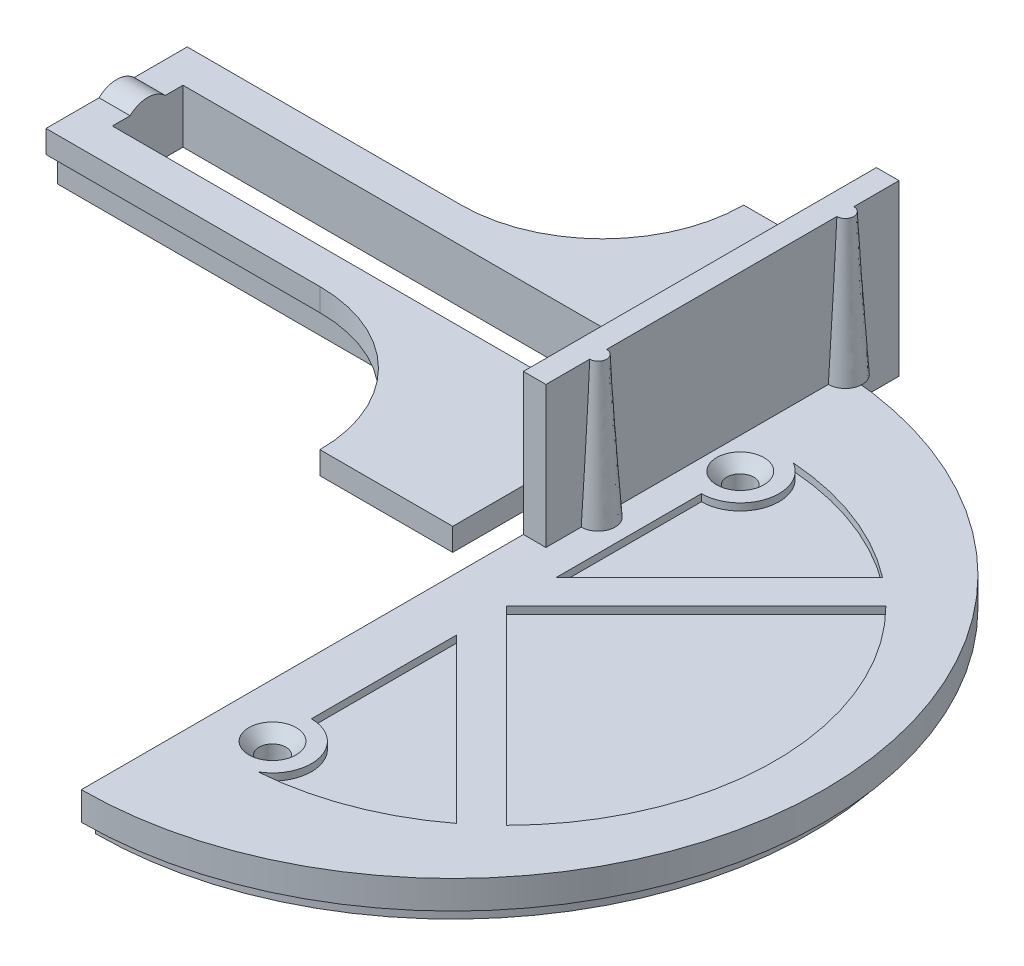
SolidWorks part; units mm, degrees
ref_plane "Alzado" through (0, 0, 0) normal (0, 0, 1) x (1, 0, 0)
ref_plane "Planta" through (0, 0, 0) normal (0, 1, 0) x (1, 0, 0)
ref_plane "Vista lateral" through (0, 0, 0) normal (1, 0, 0) x (0, 0, -1)
sketch "Sketch1" plane through (0, 0, 0) normal (1, 0, 0) x (0, 0, -1)
  line L1 (-10.668, -4.826) -> (10.668, -4.826)
  line L2 (-12.7, 0.762) -> (-12.7, 4.826)
  line L3 (-12.7, 4.826) -> (-3.1623, 4.826)
  line L6 (0, -4.826) -> (0, 12.0832) construction
  line L7 (-10.668, -4.826) -> (-10.668, 0.762)
  line L9 (-10.668, 0.762) -> (-12.7, 0.762)
  line L13 (10.668, 0.762) -> (12.7, 0.762)
  line L14 (10.668, -4.826) -> (10.668, 0.762)
  line L15 (12.7, 4.826) -> (3.1623, 4.826)
  line L16 (12.7, 0.762) -> (12.7, 4.826)
  arc A0 (3.1623, 4.826) -> (-3.1623, 4.826) centre (0, 1.524) ccw
  point P0 (0, 0)
  dimension "D5" = 9.144
extrude "Boss-Extrude1" add sketch "Sketch1" along normal blind 98.552
sketch "Sketch2" plane through (0, 4.826, 0) normal (0, 1, 0) x (1, 0, 0)
  line L0 (0, 0) -> (5.588, 0)
  line L1 (5.588, -6.35) -> (5.588, 6.35)
  line L2 (5.588, 6.35) -> (98.552, 6.35)
  line L3 (98.552, 12.7) -> (98.552, 3.1623) construction
  line L4 (5.588, -6.35) -> (98.552, -6.35)
  line L5 (98.552, -3.1623) -> (98.552, -12.7) construction
  line L6 (98.552, -6.35) -> (98.552, 6.35)
  point P6 (5.588, 0)
  line M6 (98.552, -12.7) -> (98.552, -3.1623)
  line M7 (98.552, -3.1623) -> (0, -3.1623)
  dimension "D1" = 5.588
  dimension "D2" = 12.7
extrude "Cut-Extrude2" cut sketch "Sketch2" against normal through all both and the other way through all contours L1 L4 M6 M7 | L6 L2 L1 M7 region at (52.07, 4.826, -1.5939) region at (52.07, 4.826, 4.7561)
sketch "Sketch3" plane through (0, 4.826, 0) normal (0, 1, 0) x (1, 0, 0)
  line L0 (0, -12.7) -> (49.276, -12.7)
  line L1 (98.552, -12.7) -> (0, -12.7) construction
  line L2 (49.276, -12.7) -> (98.552, -12.7)
  line L3 (98.552, -12.7) -> (98.552, -38.1)
  line L4 (98.552, -38.1) -> (74.676, -38.1)
  arc A0 (74.676, -38.1) -> (49.276, -12.7) centre (49.276, -38.1) ccw
  line M6 (0, -12.7) -> (98.552, -12.7)
  dimension "D2" = 50.8
  dimension "D1" = 49.276
extrude "Boss-Extrude2" add sketch "Sketch3" against normal up to vertex (4.064 mm away) contours A0 L4 L3 M6 region at (83.3406, 4.826, 24.094) up to point (98.552, 0.762, 12.7)
mirror "Mirror1" about plane through (0, 0, 0) normal (0, 0, 1) of "Boss-Extrude2"
sketch "Sketch9" plane through (5.588, 0, 0) normal (1, 0, 0) x (0, 0, -1)
  line L0 (-6.35, -4.826) -> (6.35, -4.826) construction
  circle A0 centre (0, 1.524) radius 3.683
  dimension "D2" = 7.366
  dimension "D1" = 6.35
sketch "Sketch10" plane through (0, 0, -38.1) normal (0, 0, -1) x (-1, 0, 0)
  line L0 (-98.552, 0.762) -> (-102.616, 0.762)
  line L1 (-102.616, 0.762) -> (-102.616, -7.874)
  line L2 (-102.616, -7.874) -> (-98.552, -7.874)
  line L3 (-98.552, -7.874) -> (-98.552, 22.606)
  line L4 (-98.552, 22.606) -> (-102.616, 22.606)
  line L5 (-102.616, 22.606) -> (-102.616, 0.762)
  line M5 (-98.552, 4.826) -> (-98.552, 0.762)
  dimension "D1" = 4.064
  dimension "D2" = 8.636
  dimension "D3" = 30.48
extrude "Boss-Extrude3" add sketch "Sketch10" against normal blind 63.5 contours L4 L5 L0 L3 M5 | L2 L3 L0 L1 region at (100.584, -3.556, -38.1) region at (100.584, 11.684, -38.1)
sketch "Sketch11" plane through (102.616, 0, 0) normal (1, 0, 0) x (0, 0, -1)
  line L0 (-25.4, 22.606) -> (-25.4, -2.794)
  line L1 (-25.4, 22.606) -> (-25.4, -7.874) construction
  point P6 (-25.4, -2.794)
  dimension "D1" = 25.4
ref_plane "Plane1" through (0, -2.794, 0) normal (0, -1, 0) x (-1, 0, 0)
sketch "Sketch12" plane through (0, -2.794, 0) normal (0, -1, 0) x (-1, 0, 0)
  line L0 (-98.552, -25.4) -> (-98.552, -26.0678)
  line L3 (-98.552, -38.1) -> (-74.676, -38.1) construction
  line L4 (-98.552, -38.1) -> (-98.552, 28.702) construction
  line L5 (-98.552, -38.1) -> (-98.552, -104.902) construction
  arc A0 (-98.552, -25.4) -> (-98.552, -50.8) centre (-98.552, -38.1) ccw
  arc A1 (-98.552, -31.75) -> (-98.552, -44.45) centre (-98.552, -38.1) ccw
  arc A2 (-98.552, 28.702) -> (-98.552, -104.902) centre (-98.552, -38.1) ccw
  point P4 (0, 0)
  point P10 (-98.552, -38.1)
  dimension "D1" = 25.4
  dimension "D2" = 12.7
  dimension "D3" = 133.604
sketch "Sketch14" plane through (0, 22.606, 0) normal (0, 1, 0) x (1, 0, 0)
  line L0 (102.616, -25.4) -> (102.616, 38.1) construction
  circle A0 centre (102.616, 28.448) radius 1.524
  circle A1 centre (102.616, -16.002) radius 1.524
  dimension "D1" = 3.048
  dimension "D2" = 9.652
  dimension "D3" = 44.45
sketch "Sketch15" plane through (0, -2.794, 0) normal (0, -1, 0) x (-1, 0, 0)
  circle A0 centre (-102.616, 28.448) radius 3.048
  circle A1 centre (-102.616, -16.002) radius 3.048
  dimension "D1" = 6.096
loft "Loft1" add section "Sketch14" section "Sketch15" connector at (104.1369, 22.606, -28.3514) connector at (105.2998, -2.794, -27.0032)
loft "Loft2" add section "Sketch14<4>" section "Sketch15<5>" connector at (104.1286, 22.606, 16.1883) connector at (105.4429, -2.794, 14.8622)
sketch "Sketch14<4>" plane through (0, 22.606, 0) normal (0, 1, 0) x (1, 0, 0) same geometry as "Sketch14"
sketch "Sketch15<5>" plane through (0, -2.794, 0) normal (0, -1, 0) x (-1, 0, 0) same geometry as "Sketch15"
ref_plane "Plane3" through (108.204, 0, 0) normal (-1, 0, 0) x (0, 0, 1)
sketch "Sketch17" plane through (98.552, 0, 0) normal (-1, 0, 0) x (0, 0, 1)
  line L0 (38.1, -2.794) -> (38.1, -6.096) construction
  line L1 (-26.162, -10.922) -> (-23.114, -10.922)
  line L2 (38.1, -6.096) -> (31.5895, -6.096)
  line L3 (31.5895, -6.096) -> (31.5895, -9.144)
  line L4 (31.5895, -9.144) -> (22.3837, -9.144)
  line L5 (22.3837, -9.144) -> (22.3837, -7.874)
  line L6 (25.4, -7.874) -> (-38.1, -7.874) construction
  line L7 (22.3837, -7.874) -> (-8.636, -7.874)
  line L8 (-8.636, -7.874) -> (-8.636, -9.398)
  line L9 (-8.636, -9.398) -> (-14.986, -9.398)
  line L10 (-14.986, -9.398) -> (-14.986, -7.874)
  line L11 (-14.986, -7.874) -> (-23.114, -7.874)
  line L12 (-23.114, -7.874) -> (-23.114, -10.922)
  line L14 (38.1, -2.794) -> (-28.702, -2.794)
  line L15 (-28.702, -2.794) -> (-28.702, -7.874)
  line L16 (38.1, -6.096) -> (38.1, -2.794)
  line L17 (-26.162, -10.922) -> (-26.162, -7.874)
  line L18 (-26.162, -7.874) -> (-28.702, -7.874)
  point P1 (-26.162, -10.922)
  dimension "D1" = 3.048
  dimension "D2" = 6.35
  dimension "D3" = 66.802
  dimension "D4" = 6.35
  dimension "D5" = 1.524
  dimension "D6" = 61.214
  dimension "D7" = 3.048
  dimension "D8" = 46.736
  dimension "D9" = 64.262
revolve "Revolve1" add sketch "Sketch17" angle 180 about L16 reverse direction yes
sketch "Sketch19" plane through (0, -2.794, 0) normal (0, 1, 0) x (1, 0, 0)
  line L4 (108.204, 16.764) -> (108.204, -16.764) construction
  line L6 (108.204, -38.1) -> (142.329, -72.225)
  line L7 (108.204, -47.0803) -> (137.5422, -76.4184)
  line L8 (108.204, -47.0803) -> (108.204, -73.1774)
  line L9 (98.552, -38.1) -> (98.552, -104.902) construction
  line L10 (108.204, -38.1) -> (142.329, -3.975)
  line L11 (108.204, -29.1197) -> (137.5422, 0.2184)
  line L12 (108.204, -29.1197) -> (108.204, -3.0226)
  arc A6 (111.6528, -86.2366) -> (137.5422, -76.4184) centre (108.204, -38.1) ccw
  arc A7 (111.6528, 10.0366) -> (108.204, -3.0226) centre (108.204, 3.9624) cw
  arc A8 (137.5422, 0.2184) -> (111.6528, 10.0366) centre (108.204, -38.1) ccw
  arc A9 (111.6528, -86.2366) -> (108.204, -73.1774) centre (108.204, -80.1624) ccw
  arc A10 (142.329, -72.225) -> (142.329, -3.975) centre (108.204, -38.1) ccw
  point P0 (98.552, -38.1)
  point P10 (0, 0)
  dimension "D2" = 6.35
  dimension "D1" = 96.52
  dimension "D4" = 13.97
  dimension "D3" = 45
  dimension "D5" = 42.0624
  dimension "D6" = 9.652
extrude "Cut-Extrude3" cut sketch "Sketch19" against normal blind 1.27
hole_wizard "CSK for #1 Flat Head Socket Cap Screw1" positions "Sketch20" profile "Sketch21" countersink size "#1" standard "ANSI Inch" end condition through all
sketch "Sketch20" plane through (0, -2.794, 0) normal (0, 1, 0) x (1, 0, 0)
  arc A0 (108.204, -3.0226) -> (111.6528, 10.0366) centre (108.204, 3.9624) ccw construction
  point P0 (108.204, -80.1624)
  point P3 (108.204, 3.9624)
  point P7 (0, 0)
sketch "Sketch21" plane through (108.204, -2.794, 80.1624) normal (1, 0, 0) x (0, 0, 1)
  line L0 (0, 0) -> (0, 8.128)
  line L1 (0, 8.128) -> (2.413, 8.128)
  line L2 (2.413, 8.128) -> (2.413, 2.1184)
  line L3 (2.413, 2.1184) -> (4.2545, 0)
  line L5 (4.2545, 0) -> (0, 0)
  line L6 (-2.413, 2.1184) -> (-4.2545, 0) construction
  line L11 (0, -6.35) -> (0, 107.95) construction
  dimension "Thru Hole Dia." = 4.826
  dimension "Thru Hole Depth" = 8.128
  dimension "Near C'Sink Dia." = 8.509
  dimension "Near C'Sink Angle" = 82
